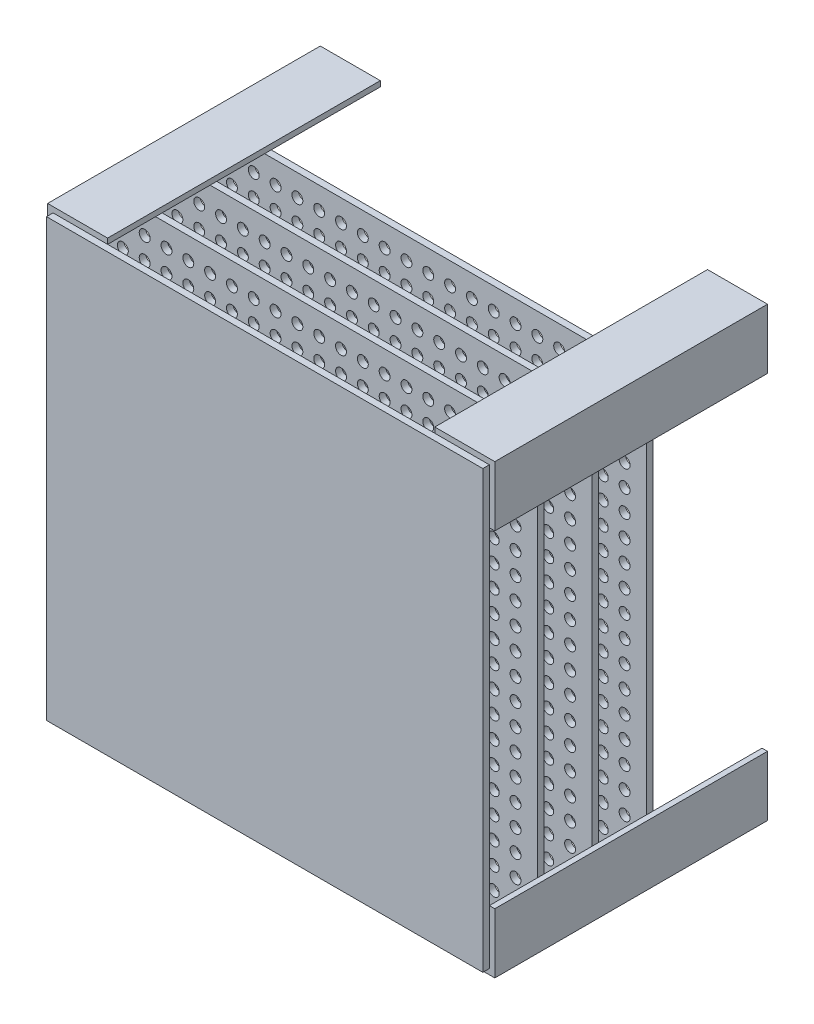
SolidWorks part; units mm, degrees
material "ASTM A36 Steel"
ref_plane "Front Plane" through (0, 0, 0) normal (0, 0, 1) x (1, 0, 0)
ref_plane "Top Plane" through (0, 0, 0) normal (0, 1, 0) x (1, 0, 0)
ref_plane "Right Plane" through (0, 0, 0) normal (1, 0, 0) x (0, 0, -1)
sketch "Sketch1" plane through (0, 0, 0) normal (0, 0, 1) x (1, 0, 0)
  line L1 (-200, 200) -> (200, 200)
  line L2 (-200, 200) -> (-200, -200)
  line L3 (-200, -200) -> (200, -200)
  line L4 (200, 200) -> (200, -200)
  line L5 (-200, 200) -> (200, -200) construction
  line L6 (-200, -200) -> (200, 200) construction
  line L10 (-180, 160) -> (180, 160) construction
  circle A0 centre (-180, 180) radius 5
  circle A1 centre (-160, 180) radius 5
  circle A2 centre (-140, 180) radius 5
  circle A3 centre (-120, 180) radius 5
  circle A4 centre (-100, 180) radius 5
  circle A5 centre (-80, 180) radius 5
  circle A6 centre (-60, 180) radius 5
  circle A7 centre (-40, 180) radius 5
  circle A8 centre (-20, 180) radius 5
  circle A9 centre (0, 180) radius 5
  circle A10 centre (20, 180) radius 5
  circle A11 centre (40, 180) radius 5
  circle A12 centre (60, 180) radius 5
  circle A13 centre (80, 180) radius 5
  circle A14 centre (100, 180) radius 5
  circle A15 centre (120, 180) radius 5
  circle A16 centre (140, 180) radius 5
  circle A17 centre (160, 180) radius 5
  circle A18 centre (180, 180) radius 5
  circle A19 centre (-180, 160) radius 5
  circle A20 centre (-160, 160) radius 5
  circle A21 centre (-140, 160) radius 5
  circle A22 centre (-120, 160) radius 5
  circle A23 centre (-100, 160) radius 5
  circle A24 centre (-80, 160) radius 5
  circle A25 centre (-60, 160) radius 5
  circle A26 centre (-40, 160) radius 5
  circle A27 centre (-20, 160) radius 5
  circle A28 centre (0, 160) radius 5
  circle A29 centre (20, 160) radius 5
  circle A30 centre (40, 160) radius 5
  circle A31 centre (60, 160) radius 5
  circle A32 centre (80, 160) radius 5
  circle A33 centre (100, 160) radius 5
  circle A34 centre (120, 160) radius 5
  circle A35 centre (140, 160) radius 5
  circle A36 centre (160, 160) radius 5
  circle A37 centre (180, 160) radius 5
  circle A38 centre (-180, 140) radius 5
  circle A39 centre (-160, 140) radius 5
  circle A40 centre (-140, 140) radius 5
  circle A41 centre (-120, 140) radius 5
  circle A42 centre (-100, 140) radius 5
  circle A43 centre (-80, 140) radius 5
  circle A44 centre (-60, 140) radius 5
  circle A45 centre (-40, 140) radius 5
  circle A46 centre (-20, 140) radius 5
  circle A47 centre (0, 140) radius 5
  circle A48 centre (20, 140) radius 5
  circle A49 centre (40, 140) radius 5
  circle A50 centre (60, 140) radius 5
  circle A51 centre (80, 140) radius 5
  circle A52 centre (100, 140) radius 5
  circle A53 centre (120, 140) radius 5
  circle A54 centre (140, 140) radius 5
  circle A55 centre (160, 140) radius 5
  circle A56 centre (180, 140) radius 5
  circle A57 centre (-180, 120) radius 5
  circle A58 centre (-160, 120) radius 5
  circle A59 centre (-140, 120) radius 5
  circle A60 centre (-120, 120) radius 5
  circle A61 centre (-100, 120) radius 5
  circle A62 centre (-80, 120) radius 5
  circle A63 centre (-60, 120) radius 5
  circle A64 centre (-40, 120) radius 5
  circle A65 centre (-20, 120) radius 5
  circle A66 centre (0, 120) radius 5
  circle A67 centre (20, 120) radius 5
  circle A68 centre (40, 120) radius 5
  circle A69 centre (60, 120) radius 5
  circle A70 centre (80, 120) radius 5
  circle A71 centre (100, 120) radius 5
  circle A72 centre (120, 120) radius 5
  circle A73 centre (140, 120) radius 5
  circle A74 centre (160, 120) radius 5
  circle A75 centre (180, 120) radius 5
  circle A76 centre (-180, 100) radius 5
  circle A77 centre (-160, 100) radius 5
  circle A78 centre (-140, 100) radius 5
  circle A79 centre (-120, 100) radius 5
  circle A80 centre (-100, 100) radius 5
  circle A81 centre (-80, 100) radius 5
  circle A82 centre (-60, 100) radius 5
  circle A83 centre (-40, 100) radius 5
  circle A84 centre (-20, 100) radius 5
  circle A85 centre (0, 100) radius 5
  circle A86 centre (20, 100) radius 5
  circle A87 centre (40, 100) radius 5
  circle A88 centre (60, 100) radius 5
  circle A89 centre (80, 100) radius 5
  circle A90 centre (100, 100) radius 5
  circle A91 centre (120, 100) radius 5
  circle A92 centre (140, 100) radius 5
  circle A93 centre (160, 100) radius 5
  circle A94 centre (180, 100) radius 5
  circle A95 centre (-180, 80) radius 5
  circle A96 centre (-160, 80) radius 5
  circle A97 centre (-140, 80) radius 5
  circle A98 centre (-120, 80) radius 5
  circle A99 centre (-100, 80) radius 5
  circle A100 centre (-80, 80) radius 5
  circle A101 centre (-60, 80) radius 5
  circle A102 centre (-40, 80) radius 5
  circle A103 centre (-20, 80) radius 5
  circle A104 centre (0, 80) radius 5
  circle A105 centre (20, 80) radius 5
  circle A106 centre (40, 80) radius 5
  circle A107 centre (60, 80) radius 5
  circle A108 centre (80, 80) radius 5
  circle A109 centre (100, 80) radius 5
  circle A110 centre (120, 80) radius 5
  circle A111 centre (140, 80) radius 5
  circle A112 centre (160, 80) radius 5
  circle A113 centre (180, 80) radius 5
  circle A114 centre (-180, 60) radius 5
  circle A115 centre (-160, 60) radius 5
  circle A116 centre (-140, 60) radius 5
  circle A117 centre (-120, 60) radius 5
  circle A118 centre (-100, 60) radius 5
  circle A119 centre (-80, 60) radius 5
  circle A120 centre (-60, 60) radius 5
  circle A121 centre (-40, 60) radius 5
  circle A122 centre (-20, 60) radius 5
  circle A123 centre (0, 60) radius 5
  circle A124 centre (20, 60) radius 5
  circle A125 centre (40, 60) radius 5
  circle A126 centre (60, 60) radius 5
  circle A127 centre (80, 60) radius 5
  circle A128 centre (100, 60) radius 5
  circle A129 centre (120, 60) radius 5
  circle A130 centre (140, 60) radius 5
  circle A131 centre (160, 60) radius 5
  circle A132 centre (180, 60) radius 5
  circle A133 centre (-180, 40) radius 5
  circle A134 centre (-160, 40) radius 5
  circle A135 centre (-140, 40) radius 5
  circle A136 centre (-120, 40) radius 5
  circle A137 centre (-100, 40) radius 5
  circle A138 centre (-80, 40) radius 5
  circle A139 centre (-60, 40) radius 5
  circle A140 centre (-40, 40) radius 5
  circle A141 centre (-20, 40) radius 5
  circle A142 centre (0, 40) radius 5
  circle A143 centre (20, 40) radius 5
  circle A144 centre (40, 40) radius 5
  circle A145 centre (60, 40) radius 5
  circle A146 centre (80, 40) radius 5
  circle A147 centre (100, 40) radius 5
  circle A148 centre (120, 40) radius 5
  circle A149 centre (140, 40) radius 5
  circle A150 centre (160, 40) radius 5
  circle A151 centre (180, 40) radius 5
  circle A152 centre (-180, 20) radius 5
  circle A153 centre (-160, 20) radius 5
  circle A154 centre (-140, 20) radius 5
  circle A155 centre (-120, 20) radius 5
  circle A156 centre (-100, 20) radius 5
  circle A157 centre (-80, 20) radius 5
  circle A158 centre (-60, 20) radius 5
  circle A159 centre (-40, 20) radius 5
  circle A160 centre (-20, 20) radius 5
  circle A161 centre (0, 20) radius 5
  circle A162 centre (20, 20) radius 5
  circle A163 centre (40, 20) radius 5
  circle A164 centre (60, 20) radius 5
  circle A165 centre (80, 20) radius 5
  circle A166 centre (100, 20) radius 5
  circle A167 centre (120, 20) radius 5
  circle A168 centre (140, 20) radius 5
  circle A169 centre (160, 20) radius 5
  circle A170 centre (180, 20) radius 5
  circle A171 centre (-180, 0) radius 5
  circle A172 centre (-160, 0) radius 5
  circle A173 centre (-140, 0) radius 5
  circle A174 centre (-120, 0) radius 5
  circle A175 centre (-100, 0) radius 5
  circle A176 centre (-80, 0) radius 5
  circle A177 centre (-60, 0) radius 5
  circle A178 centre (-40, 0) radius 5
  circle A179 centre (-20, 0) radius 5
  circle A180 centre (0, 0) radius 5
  circle A181 centre (20, 0) radius 5
  circle A182 centre (40, 0) radius 5
  circle A183 centre (60, 0) radius 5
  circle A184 centre (80, 0) radius 5
  circle A185 centre (100, 0) radius 5
  circle A186 centre (120, 0) radius 5
  circle A187 centre (140, 0) radius 5
  circle A188 centre (160, 0) radius 5
  circle A189 centre (180, 0) radius 5
  circle A190 centre (-180, -20) radius 5
  circle A191 centre (-160, -20) radius 5
  circle A192 centre (-140, -20) radius 5
  circle A193 centre (-120, -20) radius 5
  circle A194 centre (-100, -20) radius 5
  circle A195 centre (-80, -20) radius 5
  circle A196 centre (-60, -20) radius 5
  circle A197 centre (-40, -20) radius 5
  circle A198 centre (-20, -20) radius 5
  circle A199 centre (0, -20) radius 5
  circle A200 centre (20, -20) radius 5
  circle A201 centre (40, -20) radius 5
  circle A202 centre (60, -20) radius 5
  circle A203 centre (80, -20) radius 5
  circle A204 centre (100, -20) radius 5
  circle A205 centre (120, -20) radius 5
  circle A206 centre (140, -20) radius 5
  circle A207 centre (160, -20) radius 5
  circle A208 centre (180, -20) radius 5
  circle A209 centre (-180, -40) radius 5
  circle A210 centre (-160, -40) radius 5
  circle A211 centre (-140, -40) radius 5
  circle A212 centre (-120, -40) radius 5
  circle A213 centre (-100, -40) radius 5
  circle A214 centre (-80, -40) radius 5
  circle A215 centre (-60, -40) radius 5
  circle A216 centre (-40, -40) radius 5
  circle A217 centre (-20, -40) radius 5
  circle A218 centre (0, -40) radius 5
  circle A219 centre (20, -40) radius 5
  circle A220 centre (40, -40) radius 5
  circle A221 centre (60, -40) radius 5
  circle A222 centre (80, -40) radius 5
  circle A223 centre (100, -40) radius 5
  circle A224 centre (120, -40) radius 5
  circle A225 centre (140, -40) radius 5
  circle A226 centre (160, -40) radius 5
  circle A227 centre (180, -40) radius 5
  circle A228 centre (-180, -60) radius 5
  circle A229 centre (-160, -60) radius 5
  circle A230 centre (-140, -60) radius 5
  circle A231 centre (-120, -60) radius 5
  circle A232 centre (-100, -60) radius 5
  circle A233 centre (-80, -60) radius 5
  circle A234 centre (-60, -60) radius 5
  circle A235 centre (-40, -60) radius 5
  circle A236 centre (-20, -60) radius 5
  circle A237 centre (0, -60) radius 5
  circle A238 centre (20, -60) radius 5
  circle A239 centre (40, -60) radius 5
  circle A240 centre (60, -60) radius 5
  circle A241 centre (80, -60) radius 5
  circle A242 centre (100, -60) radius 5
  circle A243 centre (120, -60) radius 5
  circle A244 centre (140, -60) radius 5
  circle A245 centre (160, -60) radius 5
  circle A246 centre (180, -60) radius 5
  circle A247 centre (-180, -80) radius 5
  circle A248 centre (-160, -80) radius 5
  circle A249 centre (-140, -80) radius 5
  circle A250 centre (-120, -80) radius 5
  circle A251 centre (-100, -80) radius 5
  circle A252 centre (-80, -80) radius 5
  circle A253 centre (-60, -80) radius 5
  circle A254 centre (-40, -80) radius 5
  circle A255 centre (-20, -80) radius 5
  circle A256 centre (0, -80) radius 5
  circle A257 centre (20, -80) radius 5
  circle A258 centre (40, -80) radius 5
  circle A259 centre (60, -80) radius 5
  circle A260 centre (80, -80) radius 5
  circle A261 centre (100, -80) radius 5
  circle A262 centre (120, -80) radius 5
  circle A263 centre (140, -80) radius 5
  circle A264 centre (160, -80) radius 5
  circle A265 centre (180, -80) radius 5
  circle A266 centre (-180, -100) radius 5
  circle A267 centre (-160, -100) radius 5
  circle A268 centre (-140, -100) radius 5
  circle A269 centre (-120, -100) radius 5
  circle A270 centre (-100, -100) radius 5
  circle A271 centre (-80, -100) radius 5
  circle A272 centre (-60, -100) radius 5
  circle A273 centre (-40, -100) radius 5
  circle A274 centre (-20, -100) radius 5
  circle A275 centre (0, -100) radius 5
  circle A276 centre (20, -100) radius 5
  circle A277 centre (40, -100) radius 5
  circle A278 centre (60, -100) radius 5
  circle A279 centre (80, -100) radius 5
  circle A280 centre (100, -100) radius 5
  circle A281 centre (120, -100) radius 5
  circle A282 centre (140, -100) radius 5
  circle A283 centre (160, -100) radius 5
  circle A284 centre (180, -100) radius 5
  circle A285 centre (-180, -120) radius 5
  circle A286 centre (-160, -120) radius 5
  circle A287 centre (-140, -120) radius 5
  circle A288 centre (-120, -120) radius 5
  circle A289 centre (-100, -120) radius 5
  circle A290 centre (-80, -120) radius 5
  circle A291 centre (-60, -120) radius 5
  circle A292 centre (-40, -120) radius 5
  circle A293 centre (-20, -120) radius 5
  circle A294 centre (0, -120) radius 5
  circle A295 centre (20, -120) radius 5
  circle A296 centre (40, -120) radius 5
  circle A297 centre (60, -120) radius 5
  circle A298 centre (80, -120) radius 5
  circle A299 centre (100, -120) radius 5
  circle A300 centre (120, -120) radius 5
  circle A301 centre (140, -120) radius 5
  circle A302 centre (160, -120) radius 5
  circle A303 centre (180, -120) radius 5
  circle A304 centre (-180, -140) radius 5
  circle A305 centre (-160, -140) radius 5
  circle A306 centre (-140, -140) radius 5
  circle A307 centre (-120, -140) radius 5
  circle A308 centre (-100, -140) radius 5
  circle A309 centre (-80, -140) radius 5
  circle A310 centre (-60, -140) radius 5
  circle A311 centre (-40, -140) radius 5
  circle A312 centre (-20, -140) radius 5
  circle A313 centre (0, -140) radius 5
  circle A314 centre (20, -140) radius 5
  circle A315 centre (40, -140) radius 5
  circle A316 centre (60, -140) radius 5
  circle A317 centre (80, -140) radius 5
  circle A318 centre (100, -140) radius 5
  circle A319 centre (120, -140) radius 5
  circle A320 centre (140, -140) radius 5
  circle A321 centre (160, -140) radius 5
  circle A322 centre (180, -140) radius 5
  circle A323 centre (-180, -160) radius 5
  circle A324 centre (-160, -160) radius 5
  circle A325 centre (-140, -160) radius 5
  circle A326 centre (-120, -160) radius 5
  circle A327 centre (-100, -160) radius 5
  circle A328 centre (-80, -160) radius 5
  circle A329 centre (-60, -160) radius 5
  circle A330 centre (-40, -160) radius 5
  circle A331 centre (-20, -160) radius 5
  circle A332 centre (0, -160) radius 5
  circle A333 centre (20, -160) radius 5
  circle A334 centre (40, -160) radius 5
  circle A335 centre (60, -160) radius 5
  circle A336 centre (80, -160) radius 5
  circle A337 centre (100, -160) radius 5
  circle A338 centre (120, -160) radius 5
  circle A339 centre (140, -160) radius 5
  circle A340 centre (160, -160) radius 5
  circle A341 centre (180, -160) radius 5
  circle A342 centre (-180, -180) radius 5
  circle A343 centre (-160, -180) radius 5
  circle A344 centre (-140, -180) radius 5
  circle A345 centre (-120, -180) radius 5
  circle A346 centre (-100, -180) radius 5
  circle A347 centre (-80, -180) radius 5
  circle A348 centre (-60, -180) radius 5
  circle A349 centre (-40, -180) radius 5
  circle A350 centre (-20, -180) radius 5
  circle A351 centre (0, -180) radius 5
  circle A352 centre (20, -180) radius 5
  circle A353 centre (40, -180) radius 5
  circle A354 centre (60, -180) radius 5
  circle A355 centre (80, -180) radius 5
  circle A356 centre (100, -180) radius 5
  circle A357 centre (120, -180) radius 5
  circle A358 centre (140, -180) radius 5
  circle A359 centre (160, -180) radius 5
  circle A360 centre (180, -180) radius 5
  point P0 (0, 0)
  dimension "D3" = 10
  dimension "D1" = 400
  dimension "D4" = 19
  dimension "D6" = 19
extrude "Boss-Extrude1" add sketch "Sketch1" along normal blind 6
ref_plane "Plane4" through (0, 0, 50) normal (0, 0, 1) x (1, 0, 0)
sketch "Sketch4" plane through (0, 0, 50) normal (0, 0, 1) x (1, 0, 0)
  line L1 (-200, 200) -> (200, 200)
  line L2 (-200, 200) -> (-200, -200)
  line L3 (-200, -200) -> (200, -200)
  line L4 (200, 200) -> (200, -200)
  line L5 (-200, 200) -> (200, -200) construction
  line L6 (-200, -200) -> (200, 200) construction
  line L10 (-180, 160) -> (180, 160) construction
  circle A0 centre (-180, 180) radius 5
  circle A1 centre (-160, 180) radius 5
  circle A2 centre (-140, 180) radius 5
  circle A3 centre (-120, 180) radius 5
  circle A4 centre (-100, 180) radius 5
  circle A5 centre (-80, 180) radius 5
  circle A6 centre (-60, 180) radius 5
  circle A7 centre (-40, 180) radius 5
  circle A8 centre (-20, 180) radius 5
  circle A9 centre (0, 180) radius 5
  circle A10 centre (20, 180) radius 5
  circle A11 centre (40, 180) radius 5
  circle A12 centre (60, 180) radius 5
  circle A13 centre (80, 180) radius 5
  circle A14 centre (100, 180) radius 5
  circle A15 centre (120, 180) radius 5
  circle A16 centre (140, 180) radius 5
  circle A17 centre (160, 180) radius 5
  circle A18 centre (180, 180) radius 5
  circle A19 centre (-180, 160) radius 5
  circle A20 centre (-160, 160) radius 5
  circle A21 centre (-140, 160) radius 5
  circle A22 centre (-120, 160) radius 5
  circle A23 centre (-100, 160) radius 5
  circle A24 centre (-80, 160) radius 5
  circle A25 centre (-60, 160) radius 5
  circle A26 centre (-40, 160) radius 5
  circle A27 centre (-20, 160) radius 5
  circle A28 centre (0, 160) radius 5
  circle A29 centre (20, 160) radius 5
  circle A30 centre (40, 160) radius 5
  circle A31 centre (60, 160) radius 5
  circle A32 centre (80, 160) radius 5
  circle A33 centre (100, 160) radius 5
  circle A34 centre (120, 160) radius 5
  circle A35 centre (140, 160) radius 5
  circle A36 centre (160, 160) radius 5
  circle A37 centre (180, 160) radius 5
  circle A38 centre (-180, 140) radius 5
  circle A39 centre (-160, 140) radius 5
  circle A40 centre (-140, 140) radius 5
  circle A41 centre (-120, 140) radius 5
  circle A42 centre (-100, 140) radius 5
  circle A43 centre (-80, 140) radius 5
  circle A44 centre (-60, 140) radius 5
  circle A45 centre (-40, 140) radius 5
  circle A46 centre (-20, 140) radius 5
  circle A47 centre (0, 140) radius 5
  circle A48 centre (20, 140) radius 5
  circle A49 centre (40, 140) radius 5
  circle A50 centre (60, 140) radius 5
  circle A51 centre (80, 140) radius 5
  circle A52 centre (100, 140) radius 5
  circle A53 centre (120, 140) radius 5
  circle A54 centre (140, 140) radius 5
  circle A55 centre (160, 140) radius 5
  circle A56 centre (180, 140) radius 5
  circle A57 centre (-180, 120) radius 5
  circle A58 centre (-160, 120) radius 5
  circle A59 centre (-140, 120) radius 5
  circle A60 centre (-120, 120) radius 5
  circle A61 centre (-100, 120) radius 5
  circle A62 centre (-80, 120) radius 5
  circle A63 centre (-60, 120) radius 5
  circle A64 centre (-40, 120) radius 5
  circle A65 centre (-20, 120) radius 5
  circle A66 centre (0, 120) radius 5
  circle A67 centre (20, 120) radius 5
  circle A68 centre (40, 120) radius 5
  circle A69 centre (60, 120) radius 5
  circle A70 centre (80, 120) radius 5
  circle A71 centre (100, 120) radius 5
  circle A72 centre (120, 120) radius 5
  circle A73 centre (140, 120) radius 5
  circle A74 centre (160, 120) radius 5
  circle A75 centre (180, 120) radius 5
  circle A76 centre (-180, 100) radius 5
  circle A77 centre (-160, 100) radius 5
  circle A78 centre (-140, 100) radius 5
  circle A79 centre (-120, 100) radius 5
  circle A80 centre (-100, 100) radius 5
  circle A81 centre (-80, 100) radius 5
  circle A82 centre (-60, 100) radius 5
  circle A83 centre (-40, 100) radius 5
  circle A84 centre (-20, 100) radius 5
  circle A85 centre (0, 100) radius 5
  circle A86 centre (20, 100) radius 5
  circle A87 centre (40, 100) radius 5
  circle A88 centre (60, 100) radius 5
  circle A89 centre (80, 100) radius 5
  circle A90 centre (100, 100) radius 5
  circle A91 centre (120, 100) radius 5
  circle A92 centre (140, 100) radius 5
  circle A93 centre (160, 100) radius 5
  circle A94 centre (180, 100) radius 5
  circle A95 centre (-180, 80) radius 5
  circle A96 centre (-160, 80) radius 5
  circle A97 centre (-140, 80) radius 5
  circle A98 centre (-120, 80) radius 5
  circle A99 centre (-100, 80) radius 5
  circle A100 centre (-80, 80) radius 5
  circle A101 centre (-60, 80) radius 5
  circle A102 centre (-40, 80) radius 5
  circle A103 centre (-20, 80) radius 5
  circle A104 centre (0, 80) radius 5
  circle A105 centre (20, 80) radius 5
  circle A106 centre (40, 80) radius 5
  circle A107 centre (60, 80) radius 5
  circle A108 centre (80, 80) radius 5
  circle A109 centre (100, 80) radius 5
  circle A110 centre (120, 80) radius 5
  circle A111 centre (140, 80) radius 5
  circle A112 centre (160, 80) radius 5
  circle A113 centre (180, 80) radius 5
  circle A114 centre (-180, 60) radius 5
  circle A115 centre (-160, 60) radius 5
  circle A116 centre (-140, 60) radius 5
  circle A117 centre (-120, 60) radius 5
  circle A118 centre (-100, 60) radius 5
  circle A119 centre (-80, 60) radius 5
  circle A120 centre (-60, 60) radius 5
  circle A121 centre (-40, 60) radius 5
  circle A122 centre (-20, 60) radius 5
  circle A123 centre (0, 60) radius 5
  circle A124 centre (20, 60) radius 5
  circle A125 centre (40, 60) radius 5
  circle A126 centre (60, 60) radius 5
  circle A127 centre (80, 60) radius 5
  circle A128 centre (100, 60) radius 5
  circle A129 centre (120, 60) radius 5
  circle A130 centre (140, 60) radius 5
  circle A131 centre (160, 60) radius 5
  circle A132 centre (180, 60) radius 5
  circle A133 centre (-180, 40) radius 5
  circle A134 centre (-160, 40) radius 5
  circle A135 centre (-140, 40) radius 5
  circle A136 centre (-120, 40) radius 5
  circle A137 centre (-100, 40) radius 5
  circle A138 centre (-80, 40) radius 5
  circle A139 centre (-60, 40) radius 5
  circle A140 centre (-40, 40) radius 5
  circle A141 centre (-20, 40) radius 5
  circle A142 centre (0, 40) radius 5
  circle A143 centre (20, 40) radius 5
  circle A144 centre (40, 40) radius 5
  circle A145 centre (60, 40) radius 5
  circle A146 centre (80, 40) radius 5
  circle A147 centre (100, 40) radius 5
  circle A148 centre (120, 40) radius 5
  circle A149 centre (140, 40) radius 5
  circle A150 centre (160, 40) radius 5
  circle A151 centre (180, 40) radius 5
  circle A152 centre (-180, 20) radius 5
  circle A153 centre (-160, 20) radius 5
  circle A154 centre (-140, 20) radius 5
  circle A155 centre (-120, 20) radius 5
  circle A156 centre (-100, 20) radius 5
  circle A157 centre (-80, 20) radius 5
  circle A158 centre (-60, 20) radius 5
  circle A159 centre (-40, 20) radius 5
  circle A160 centre (-20, 20) radius 5
  circle A161 centre (0, 20) radius 5
  circle A162 centre (20, 20) radius 5
  circle A163 centre (40, 20) radius 5
  circle A164 centre (60, 20) radius 5
  circle A165 centre (80, 20) radius 5
  circle A166 centre (100, 20) radius 5
  circle A167 centre (120, 20) radius 5
  circle A168 centre (140, 20) radius 5
  circle A169 centre (160, 20) radius 5
  circle A170 centre (180, 20) radius 5
  circle A171 centre (-180, 0) radius 5
  circle A172 centre (-160, 0) radius 5
  circle A173 centre (-140, 0) radius 5
  circle A174 centre (-120, 0) radius 5
  circle A175 centre (-100, 0) radius 5
  circle A176 centre (-80, 0) radius 5
  circle A177 centre (-60, 0) radius 5
  circle A178 centre (-40, 0) radius 5
  circle A179 centre (-20, 0) radius 5
  circle A180 centre (0, 0) radius 5
  circle A181 centre (20, 0) radius 5
  circle A182 centre (40, 0) radius 5
  circle A183 centre (60, 0) radius 5
  circle A184 centre (80, 0) radius 5
  circle A185 centre (100, 0) radius 5
  circle A186 centre (120, 0) radius 5
  circle A187 centre (140, 0) radius 5
  circle A188 centre (160, 0) radius 5
  circle A189 centre (180, 0) radius 5
  circle A190 centre (-180, -20) radius 5
  circle A191 centre (-160, -20) radius 5
  circle A192 centre (-140, -20) radius 5
  circle A193 centre (-120, -20) radius 5
  circle A194 centre (-100, -20) radius 5
  circle A195 centre (-80, -20) radius 5
  circle A196 centre (-60, -20) radius 5
  circle A197 centre (-40, -20) radius 5
  circle A198 centre (-20, -20) radius 5
  circle A199 centre (0, -20) radius 5
  circle A200 centre (20, -20) radius 5
  circle A201 centre (40, -20) radius 5
  circle A202 centre (60, -20) radius 5
  circle A203 centre (80, -20) radius 5
  circle A204 centre (100, -20) radius 5
  circle A205 centre (120, -20) radius 5
  circle A206 centre (140, -20) radius 5
  circle A207 centre (160, -20) radius 5
  circle A208 centre (180, -20) radius 5
  circle A209 centre (-180, -40) radius 5
  circle A210 centre (-160, -40) radius 5
  circle A211 centre (-140, -40) radius 5
  circle A212 centre (-120, -40) radius 5
  circle A213 centre (-100, -40) radius 5
  circle A214 centre (-80, -40) radius 5
  circle A215 centre (-60, -40) radius 5
  circle A216 centre (-40, -40) radius 5
  circle A217 centre (-20, -40) radius 5
  circle A218 centre (0, -40) radius 5
  circle A219 centre (20, -40) radius 5
  circle A220 centre (40, -40) radius 5
  circle A221 centre (60, -40) radius 5
  circle A222 centre (80, -40) radius 5
  circle A223 centre (100, -40) radius 5
  circle A224 centre (120, -40) radius 5
  circle A225 centre (140, -40) radius 5
  circle A226 centre (160, -40) radius 5
  circle A227 centre (180, -40) radius 5
  circle A228 centre (-180, -60) radius 5
  circle A229 centre (-160, -60) radius 5
  circle A230 centre (-140, -60) radius 5
  circle A231 centre (-120, -60) radius 5
  circle A232 centre (-100, -60) radius 5
  circle A233 centre (-80, -60) radius 5
  circle A234 centre (-60, -60) radius 5
  circle A235 centre (-40, -60) radius 5
  circle A236 centre (-20, -60) radius 5
  circle A237 centre (0, -60) radius 5
  circle A238 centre (20, -60) radius 5
  circle A239 centre (40, -60) radius 5
  circle A240 centre (60, -60) radius 5
  circle A241 centre (80, -60) radius 5
  circle A242 centre (100, -60) radius 5
  circle A243 centre (120, -60) radius 5
  circle A244 centre (140, -60) radius 5
  circle A245 centre (160, -60) radius 5
  circle A246 centre (180, -60) radius 5
  circle A247 centre (-180, -80) radius 5
  circle A248 centre (-160, -80) radius 5
  circle A249 centre (-140, -80) radius 5
  circle A250 centre (-120, -80) radius 5
  circle A251 centre (-100, -80) radius 5
  circle A252 centre (-80, -80) radius 5
  circle A253 centre (-60, -80) radius 5
  circle A254 centre (-40, -80) radius 5
  circle A255 centre (-20, -80) radius 5
  circle A256 centre (0, -80) radius 5
  circle A257 centre (20, -80) radius 5
  circle A258 centre (40, -80) radius 5
  circle A259 centre (60, -80) radius 5
  circle A260 centre (80, -80) radius 5
  circle A261 centre (100, -80) radius 5
  circle A262 centre (120, -80) radius 5
  circle A263 centre (140, -80) radius 5
  circle A264 centre (160, -80) radius 5
  circle A265 centre (180, -80) radius 5
  circle A266 centre (-180, -100) radius 5
  circle A267 centre (-160, -100) radius 5
  circle A268 centre (-140, -100) radius 5
  circle A269 centre (-120, -100) radius 5
  circle A270 centre (-100, -100) radius 5
  circle A271 centre (-80, -100) radius 5
  circle A272 centre (-60, -100) radius 5
  circle A273 centre (-40, -100) radius 5
  circle A274 centre (-20, -100) radius 5
  circle A275 centre (0, -100) radius 5
  circle A276 centre (20, -100) radius 5
  circle A277 centre (40, -100) radius 5
  circle A278 centre (60, -100) radius 5
  circle A279 centre (80, -100) radius 5
  circle A280 centre (100, -100) radius 5
  circle A281 centre (120, -100) radius 5
  circle A282 centre (140, -100) radius 5
  circle A283 centre (160, -100) radius 5
  circle A284 centre (180, -100) radius 5
  circle A285 centre (-180, -120) radius 5
  circle A286 centre (-160, -120) radius 5
  circle A287 centre (-140, -120) radius 5
  circle A288 centre (-120, -120) radius 5
  circle A289 centre (-100, -120) radius 5
  circle A290 centre (-80, -120) radius 5
  circle A291 centre (-60, -120) radius 5
  circle A292 centre (-40, -120) radius 5
  circle A293 centre (-20, -120) radius 5
  circle A294 centre (0, -120) radius 5
  circle A295 centre (20, -120) radius 5
  circle A296 centre (40, -120) radius 5
  circle A297 centre (60, -120) radius 5
  circle A298 centre (80, -120) radius 5
  circle A299 centre (100, -120) radius 5
  circle A300 centre (120, -120) radius 5
  circle A301 centre (140, -120) radius 5
  circle A302 centre (160, -120) radius 5
  circle A303 centre (180, -120) radius 5
  circle A304 centre (-180, -140) radius 5
  circle A305 centre (-160, -140) radius 5
  circle A306 centre (-140, -140) radius 5
  circle A307 centre (-120, -140) radius 5
  circle A308 centre (-100, -140) radius 5
  circle A309 centre (-80, -140) radius 5
  circle A310 centre (-60, -140) radius 5
  circle A311 centre (-40, -140) radius 5
  circle A312 centre (-20, -140) radius 5
  circle A313 centre (0, -140) radius 5
  circle A314 centre (20, -140) radius 5
  circle A315 centre (40, -140) radius 5
  circle A316 centre (60, -140) radius 5
  circle A317 centre (80, -140) radius 5
  circle A318 centre (100, -140) radius 5
  circle A319 centre (120, -140) radius 5
  circle A320 centre (140, -140) radius 5
  circle A321 centre (160, -140) radius 5
  circle A322 centre (180, -140) radius 5
  circle A323 centre (-180, -160) radius 5
  circle A324 centre (-160, -160) radius 5
  circle A325 centre (-140, -160) radius 5
  circle A326 centre (-120, -160) radius 5
  circle A327 centre (-100, -160) radius 5
  circle A328 centre (-80, -160) radius 5
  circle A329 centre (-60, -160) radius 5
  circle A330 centre (-40, -160) radius 5
  circle A331 centre (-20, -160) radius 5
  circle A332 centre (0, -160) radius 5
  circle A333 centre (20, -160) radius 5
  circle A334 centre (40, -160) radius 5
  circle A335 centre (60, -160) radius 5
  circle A336 centre (80, -160) radius 5
  circle A337 centre (100, -160) radius 5
  circle A338 centre (120, -160) radius 5
  circle A339 centre (140, -160) radius 5
  circle A340 centre (160, -160) radius 5
  circle A341 centre (180, -160) radius 5
  circle A342 centre (-180, -180) radius 5
  circle A343 centre (-160, -180) radius 5
  circle A344 centre (-140, -180) radius 5
  circle A345 centre (-120, -180) radius 5
  circle A346 centre (-100, -180) radius 5
  circle A347 centre (-80, -180) radius 5
  circle A348 centre (-60, -180) radius 5
  circle A349 centre (-40, -180) radius 5
  circle A350 centre (-20, -180) radius 5
  circle A351 centre (0, -180) radius 5
  circle A352 centre (20, -180) radius 5
  circle A353 centre (40, -180) radius 5
  circle A354 centre (60, -180) radius 5
  circle A355 centre (80, -180) radius 5
  circle A356 centre (100, -180) radius 5
  circle A357 centre (120, -180) radius 5
  circle A358 centre (140, -180) radius 5
  circle A359 centre (160, -180) radius 5
  circle A360 centre (180, -180) radius 5
  point P0 (0, 0)
  dimension "D3" = 10
  dimension "D1" = 400
  dimension "D4" = 19
  dimension "D6" = 19
extrude "Boss-Extrude3" add sketch "Sketch4" along normal blind 6 separate body
ref_plane "Plane5" through (0, 0, 100) normal (0, 0, 1) x (1, 0, 0)
sketch "Sketch6" plane through (0, 0, 100) normal (0, 0, 1) x (1, 0, 0)
  line L1 (-200, 200) -> (200, 200)
  line L2 (-200, 200) -> (-200, -200)
  line L3 (-200, -200) -> (200, -200)
  line L4 (200, 200) -> (200, -200)
  line L5 (-200, 200) -> (200, -200) construction
  line L6 (-200, -200) -> (200, 200) construction
  line L10 (-180, 160) -> (180, 160) construction
  circle A0 centre (-180, 180) radius 5
  circle A1 centre (-160, 180) radius 5
  circle A2 centre (-140, 180) radius 5
  circle A3 centre (-120, 180) radius 5
  circle A4 centre (-100, 180) radius 5
  circle A5 centre (-80, 180) radius 5
  circle A6 centre (-60, 180) radius 5
  circle A7 centre (-40, 180) radius 5
  circle A8 centre (-20, 180) radius 5
  circle A9 centre (0, 180) radius 5
  circle A10 centre (20, 180) radius 5
  circle A11 centre (40, 180) radius 5
  circle A12 centre (60, 180) radius 5
  circle A13 centre (80, 180) radius 5
  circle A14 centre (100, 180) radius 5
  circle A15 centre (120, 180) radius 5
  circle A16 centre (140, 180) radius 5
  circle A17 centre (160, 180) radius 5
  circle A18 centre (180, 180) radius 5
  circle A19 centre (-180, 160) radius 5
  circle A20 centre (-160, 160) radius 5
  circle A21 centre (-140, 160) radius 5
  circle A22 centre (-120, 160) radius 5
  circle A23 centre (-100, 160) radius 5
  circle A24 centre (-80, 160) radius 5
  circle A25 centre (-60, 160) radius 5
  circle A26 centre (-40, 160) radius 5
  circle A27 centre (-20, 160) radius 5
  circle A28 centre (0, 160) radius 5
  circle A29 centre (20, 160) radius 5
  circle A30 centre (40, 160) radius 5
  circle A31 centre (60, 160) radius 5
  circle A32 centre (80, 160) radius 5
  circle A33 centre (100, 160) radius 5
  circle A34 centre (120, 160) radius 5
  circle A35 centre (140, 160) radius 5
  circle A36 centre (160, 160) radius 5
  circle A37 centre (180, 160) radius 5
  circle A38 centre (-180, 140) radius 5
  circle A39 centre (-160, 140) radius 5
  circle A40 centre (-140, 140) radius 5
  circle A41 centre (-120, 140) radius 5
  circle A42 centre (-100, 140) radius 5
  circle A43 centre (-80, 140) radius 5
  circle A44 centre (-60, 140) radius 5
  circle A45 centre (-40, 140) radius 5
  circle A46 centre (-20, 140) radius 5
  circle A47 centre (0, 140) radius 5
  circle A48 centre (20, 140) radius 5
  circle A49 centre (40, 140) radius 5
  circle A50 centre (60, 140) radius 5
  circle A51 centre (80, 140) radius 5
  circle A52 centre (100, 140) radius 5
  circle A53 centre (120, 140) radius 5
  circle A54 centre (140, 140) radius 5
  circle A55 centre (160, 140) radius 5
  circle A56 centre (180, 140) radius 5
  circle A57 centre (-180, 120) radius 5
  circle A58 centre (-160, 120) radius 5
  circle A59 centre (-140, 120) radius 5
  circle A60 centre (-120, 120) radius 5
  circle A61 centre (-100, 120) radius 5
  circle A62 centre (-80, 120) radius 5
  circle A63 centre (-60, 120) radius 5
  circle A64 centre (-40, 120) radius 5
  circle A65 centre (-20, 120) radius 5
  circle A66 centre (0, 120) radius 5
  circle A67 centre (20, 120) radius 5
  circle A68 centre (40, 120) radius 5
  circle A69 centre (60, 120) radius 5
  circle A70 centre (80, 120) radius 5
  circle A71 centre (100, 120) radius 5
  circle A72 centre (120, 120) radius 5
  circle A73 centre (140, 120) radius 5
  circle A74 centre (160, 120) radius 5
  circle A75 centre (180, 120) radius 5
  circle A76 centre (-180, 100) radius 5
  circle A77 centre (-160, 100) radius 5
  circle A78 centre (-140, 100) radius 5
  circle A79 centre (-120, 100) radius 5
  circle A80 centre (-100, 100) radius 5
  circle A81 centre (-80, 100) radius 5
  circle A82 centre (-60, 100) radius 5
  circle A83 centre (-40, 100) radius 5
  circle A84 centre (-20, 100) radius 5
  circle A85 centre (0, 100) radius 5
  circle A86 centre (20, 100) radius 5
  circle A87 centre (40, 100) radius 5
  circle A88 centre (60, 100) radius 5
  circle A89 centre (80, 100) radius 5
  circle A90 centre (100, 100) radius 5
  circle A91 centre (120, 100) radius 5
  circle A92 centre (140, 100) radius 5
  circle A93 centre (160, 100) radius 5
  circle A94 centre (180, 100) radius 5
  circle A95 centre (-180, 80) radius 5
  circle A96 centre (-160, 80) radius 5
  circle A97 centre (-140, 80) radius 5
  circle A98 centre (-120, 80) radius 5
  circle A99 centre (-100, 80) radius 5
  circle A100 centre (-80, 80) radius 5
  circle A101 centre (-60, 80) radius 5
  circle A102 centre (-40, 80) radius 5
  circle A103 centre (-20, 80) radius 5
  circle A104 centre (0, 80) radius 5
  circle A105 centre (20, 80) radius 5
  circle A106 centre (40, 80) radius 5
  circle A107 centre (60, 80) radius 5
  circle A108 centre (80, 80) radius 5
  circle A109 centre (100, 80) radius 5
  circle A110 centre (120, 80) radius 5
  circle A111 centre (140, 80) radius 5
  circle A112 centre (160, 80) radius 5
  circle A113 centre (180, 80) radius 5
  circle A114 centre (-180, 60) radius 5
  circle A115 centre (-160, 60) radius 5
  circle A116 centre (-140, 60) radius 5
  circle A117 centre (-120, 60) radius 5
  circle A118 centre (-100, 60) radius 5
  circle A119 centre (-80, 60) radius 5
  circle A120 centre (-60, 60) radius 5
  circle A121 centre (-40, 60) radius 5
  circle A122 centre (-20, 60) radius 5
  circle A123 centre (0, 60) radius 5
  circle A124 centre (20, 60) radius 5
  circle A125 centre (40, 60) radius 5
  circle A126 centre (60, 60) radius 5
  circle A127 centre (80, 60) radius 5
  circle A128 centre (100, 60) radius 5
  circle A129 centre (120, 60) radius 5
  circle A130 centre (140, 60) radius 5
  circle A131 centre (160, 60) radius 5
  circle A132 centre (180, 60) radius 5
  circle A133 centre (-180, 40) radius 5
  circle A134 centre (-160, 40) radius 5
  circle A135 centre (-140, 40) radius 5
  circle A136 centre (-120, 40) radius 5
  circle A137 centre (-100, 40) radius 5
  circle A138 centre (-80, 40) radius 5
  circle A139 centre (-60, 40) radius 5
  circle A140 centre (-40, 40) radius 5
  circle A141 centre (-20, 40) radius 5
  circle A142 centre (0, 40) radius 5
  circle A143 centre (20, 40) radius 5
  circle A144 centre (40, 40) radius 5
  circle A145 centre (60, 40) radius 5
  circle A146 centre (80, 40) radius 5
  circle A147 centre (100, 40) radius 5
  circle A148 centre (120, 40) radius 5
  circle A149 centre (140, 40) radius 5
  circle A150 centre (160, 40) radius 5
  circle A151 centre (180, 40) radius 5
  circle A152 centre (-180, 20) radius 5
  circle A153 centre (-160, 20) radius 5
  circle A154 centre (-140, 20) radius 5
  circle A155 centre (-120, 20) radius 5
  circle A156 centre (-100, 20) radius 5
  circle A157 centre (-80, 20) radius 5
  circle A158 centre (-60, 20) radius 5
  circle A159 centre (-40, 20) radius 5
  circle A160 centre (-20, 20) radius 5
  circle A161 centre (0, 20) radius 5
  circle A162 centre (20, 20) radius 5
  circle A163 centre (40, 20) radius 5
  circle A164 centre (60, 20) radius 5
  circle A165 centre (80, 20) radius 5
  circle A166 centre (100, 20) radius 5
  circle A167 centre (120, 20) radius 5
  circle A168 centre (140, 20) radius 5
  circle A169 centre (160, 20) radius 5
  circle A170 centre (180, 20) radius 5
  circle A171 centre (-180, 0) radius 5
  circle A172 centre (-160, 0) radius 5
  circle A173 centre (-140, 0) radius 5
  circle A174 centre (-120, 0) radius 5
  circle A175 centre (-100, 0) radius 5
  circle A176 centre (-80, 0) radius 5
  circle A177 centre (-60, 0) radius 5
  circle A178 centre (-40, 0) radius 5
  circle A179 centre (-20, 0) radius 5
  circle A180 centre (0, 0) radius 5
  circle A181 centre (20, 0) radius 5
  circle A182 centre (40, 0) radius 5
  circle A183 centre (60, 0) radius 5
  circle A184 centre (80, 0) radius 5
  circle A185 centre (100, 0) radius 5
  circle A186 centre (120, 0) radius 5
  circle A187 centre (140, 0) radius 5
  circle A188 centre (160, 0) radius 5
  circle A189 centre (180, 0) radius 5
  circle A190 centre (-180, -20) radius 5
  circle A191 centre (-160, -20) radius 5
  circle A192 centre (-140, -20) radius 5
  circle A193 centre (-120, -20) radius 5
  circle A194 centre (-100, -20) radius 5
  circle A195 centre (-80, -20) radius 5
  circle A196 centre (-60, -20) radius 5
  circle A197 centre (-40, -20) radius 5
  circle A198 centre (-20, -20) radius 5
  circle A199 centre (0, -20) radius 5
  circle A200 centre (20, -20) radius 5
  circle A201 centre (40, -20) radius 5
  circle A202 centre (60, -20) radius 5
  circle A203 centre (80, -20) radius 5
  circle A204 centre (100, -20) radius 5
  circle A205 centre (120, -20) radius 5
  circle A206 centre (140, -20) radius 5
  circle A207 centre (160, -20) radius 5
  circle A208 centre (180, -20) radius 5
  circle A209 centre (-180, -40) radius 5
  circle A210 centre (-160, -40) radius 5
  circle A211 centre (-140, -40) radius 5
  circle A212 centre (-120, -40) radius 5
  circle A213 centre (-100, -40) radius 5
  circle A214 centre (-80, -40) radius 5
  circle A215 centre (-60, -40) radius 5
  circle A216 centre (-40, -40) radius 5
  circle A217 centre (-20, -40) radius 5
  circle A218 centre (0, -40) radius 5
  circle A219 centre (20, -40) radius 5
  circle A220 centre (40, -40) radius 5
  circle A221 centre (60, -40) radius 5
  circle A222 centre (80, -40) radius 5
  circle A223 centre (100, -40) radius 5
  circle A224 centre (120, -40) radius 5
  circle A225 centre (140, -40) radius 5
  circle A226 centre (160, -40) radius 5
  circle A227 centre (180, -40) radius 5
  circle A228 centre (-180, -60) radius 5
  circle A229 centre (-160, -60) radius 5
  circle A230 centre (-140, -60) radius 5
  circle A231 centre (-120, -60) radius 5
  circle A232 centre (-100, -60) radius 5
  circle A233 centre (-80, -60) radius 5
  circle A234 centre (-60, -60) radius 5
  circle A235 centre (-40, -60) radius 5
  circle A236 centre (-20, -60) radius 5
  circle A237 centre (0, -60) radius 5
  circle A238 centre (20, -60) radius 5
  circle A239 centre (40, -60) radius 5
  circle A240 centre (60, -60) radius 5
  circle A241 centre (80, -60) radius 5
  circle A242 centre (100, -60) radius 5
  circle A243 centre (120, -60) radius 5
  circle A244 centre (140, -60) radius 5
  circle A245 centre (160, -60) radius 5
  circle A246 centre (180, -60) radius 5
  circle A247 centre (-180, -80) radius 5
  circle A248 centre (-160, -80) radius 5
  circle A249 centre (-140, -80) radius 5
  circle A250 centre (-120, -80) radius 5
  circle A251 centre (-100, -80) radius 5
  circle A252 centre (-80, -80) radius 5
  circle A253 centre (-60, -80) radius 5
  circle A254 centre (-40, -80) radius 5
  circle A255 centre (-20, -80) radius 5
  circle A256 centre (0, -80) radius 5
  circle A257 centre (20, -80) radius 5
  circle A258 centre (40, -80) radius 5
  circle A259 centre (60, -80) radius 5
  circle A260 centre (80, -80) radius 5
  circle A261 centre (100, -80) radius 5
  circle A262 centre (120, -80) radius 5
  circle A263 centre (140, -80) radius 5
  circle A264 centre (160, -80) radius 5
  circle A265 centre (180, -80) radius 5
  circle A266 centre (-180, -100) radius 5
  circle A267 centre (-160, -100) radius 5
  circle A268 centre (-140, -100) radius 5
  circle A269 centre (-120, -100) radius 5
  circle A270 centre (-100, -100) radius 5
  circle A271 centre (-80, -100) radius 5
  circle A272 centre (-60, -100) radius 5
  circle A273 centre (-40, -100) radius 5
  circle A274 centre (-20, -100) radius 5
  circle A275 centre (0, -100) radius 5
  circle A276 centre (20, -100) radius 5
  circle A277 centre (40, -100) radius 5
  circle A278 centre (60, -100) radius 5
  circle A279 centre (80, -100) radius 5
  circle A280 centre (100, -100) radius 5
  circle A281 centre (120, -100) radius 5
  circle A282 centre (140, -100) radius 5
  circle A283 centre (160, -100) radius 5
  circle A284 centre (180, -100) radius 5
  circle A285 centre (-180, -120) radius 5
  circle A286 centre (-160, -120) radius 5
  circle A287 centre (-140, -120) radius 5
  circle A288 centre (-120, -120) radius 5
  circle A289 centre (-100, -120) radius 5
  circle A290 centre (-80, -120) radius 5
  circle A291 centre (-60, -120) radius 5
  circle A292 centre (-40, -120) radius 5
  circle A293 centre (-20, -120) radius 5
  circle A294 centre (0, -120) radius 5
  circle A295 centre (20, -120) radius 5
  circle A296 centre (40, -120) radius 5
  circle A297 centre (60, -120) radius 5
  circle A298 centre (80, -120) radius 5
  circle A299 centre (100, -120) radius 5
  circle A300 centre (120, -120) radius 5
  circle A301 centre (140, -120) radius 5
  circle A302 centre (160, -120) radius 5
  circle A303 centre (180, -120) radius 5
  circle A304 centre (-180, -140) radius 5
  circle A305 centre (-160, -140) radius 5
  circle A306 centre (-140, -140) radius 5
  circle A307 centre (-120, -140) radius 5
  circle A308 centre (-100, -140) radius 5
  circle A309 centre (-80, -140) radius 5
  circle A310 centre (-60, -140) radius 5
  circle A311 centre (-40, -140) radius 5
  circle A312 centre (-20, -140) radius 5
  circle A313 centre (0, -140) radius 5
  circle A314 centre (20, -140) radius 5
  circle A315 centre (40, -140) radius 5
  circle A316 centre (60, -140) radius 5
  circle A317 centre (80, -140) radius 5
  circle A318 centre (100, -140) radius 5
  circle A319 centre (120, -140) radius 5
  circle A320 centre (140, -140) radius 5
  circle A321 centre (160, -140) radius 5
  circle A322 centre (180, -140) radius 5
  circle A323 centre (-180, -160) radius 5
  circle A324 centre (-160, -160) radius 5
  circle A325 centre (-140, -160) radius 5
  circle A326 centre (-120, -160) radius 5
  circle A327 centre (-100, -160) radius 5
  circle A328 centre (-80, -160) radius 5
  circle A329 centre (-60, -160) radius 5
  circle A330 centre (-40, -160) radius 5
  circle A331 centre (-20, -160) radius 5
  circle A332 centre (0, -160) radius 5
  circle A333 centre (20, -160) radius 5
  circle A334 centre (40, -160) radius 5
  circle A335 centre (60, -160) radius 5
  circle A336 centre (80, -160) radius 5
  circle A337 centre (100, -160) radius 5
  circle A338 centre (120, -160) radius 5
  circle A339 centre (140, -160) radius 5
  circle A340 centre (160, -160) radius 5
  circle A341 centre (180, -160) radius 5
  circle A342 centre (-180, -180) radius 5
  circle A343 centre (-160, -180) radius 5
  circle A344 centre (-140, -180) radius 5
  circle A345 centre (-120, -180) radius 5
  circle A346 centre (-100, -180) radius 5
  circle A347 centre (-80, -180) radius 5
  circle A348 centre (-60, -180) radius 5
  circle A349 centre (-40, -180) radius 5
  circle A350 centre (-20, -180) radius 5
  circle A351 centre (0, -180) radius 5
  circle A352 centre (20, -180) radius 5
  circle A353 centre (40, -180) radius 5
  circle A354 centre (60, -180) radius 5
  circle A355 centre (80, -180) radius 5
  circle A356 centre (100, -180) radius 5
  circle A357 centre (120, -180) radius 5
  circle A358 centre (140, -180) radius 5
  circle A359 centre (160, -180) radius 5
  circle A360 centre (180, -180) radius 5
  point P0 (0, 0)
  dimension "D3" = 10
  dimension "D1" = 400
  dimension "D4" = 19
  dimension "D6" = 19
extrude "Boss-Extrude4" add sketch "Sketch6" along normal blind 6 separate body
ref_plane "Plane6" through (0, 0, 150) normal (0, 0, -1) x (-1, 0, 0)
sketch "Sketch8" plane through (0, 0, 150) normal (0, 0, -1) x (-1, 0, 0)
  line L1 (200, -200) -> (-200, -200)
  line L2 (200, -200) -> (200, 200)
  line L3 (200, 200) -> (-200, 200)
  line L4 (-200, -200) -> (-200, 200)
  line L5 (200, -200) -> (-200, 200) construction
  line L6 (200, 200) -> (-200, -200) construction
  point P0 (0, 0)
  dimension "D1" = 400
extrude "Boss-Extrude5" add sketch "Sketch8" against normal blind 6 separate body
sketch "Sketch9" plane through (0, 0, 150) normal (0, 0, -1) x (-1, 0, 0)
  line L0 (-150, 200) -> (-200, 200)
  line L1 (-200, 200) -> (-200, 150)
  line L2 (-150, 205) -> (-205, 205)
  line L3 (-205, 205) -> (-205, 150)
  line L4 (-150, 200) -> (-150, 205)
  line L5 (-150, 200) -> (-200, 200) construction
  line L6 (-205, 150) -> (-200, 150)
  dimension "D1" = 50
  dimension "D2" = 50
  dimension "D3" = 5
extrude "Boss-Extrude6" add sketch "Sketch9" along normal blind 250
mirror "Mirror3" about plane through (0, 0, 0) normal (1, 0, 0) of "Boss-Extrude6"
mirror "Mirror4" about plane through (0, 0, 0) normal (0, 1, 0) of "Mirror3", "Boss-Extrude6"
